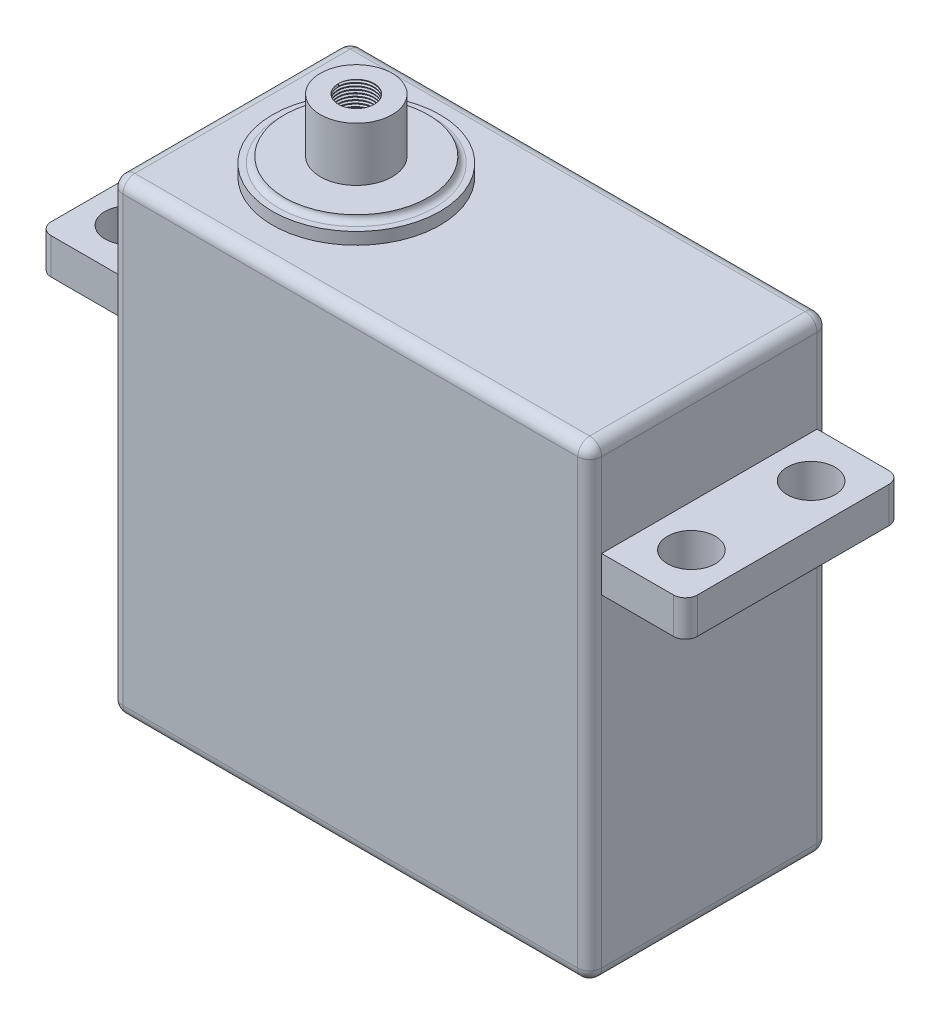
SolidWorks part; units mm, degrees
ref_plane "前视基准面" through (0, 0, 0) normal (0, 0, 1) x (1, 0, 0)
ref_plane "上视基准面" through (0, 0, 0) normal (0, 1, 0) x (1, 0, 0)
ref_plane "右视基准面" through (0, 0, 0) normal (1, 0, 0) x (0, 0, -1)
other "Configuration Table"
sketch "草图1" plane through (0, 0, 0) normal (0, 0, 1) x (1, 0, 0)
  line L1 (-18.7912, 29.9251) -> (21.2088, 29.9251)
  line L2 (-18.7912, 29.9251) -> (-18.7912, -9.0749)
  line L3 (-18.7912, -9.0749) -> (21.2088, -9.0749)
  line L4 (21.2088, 29.9251) -> (21.2088, -9.0749)
  dimension "D1" = 40
  dimension "D2" = 39
extrude "凸台-拉伸1" add sketch "草图1" along normal blind 20
fillet "圆角1" radius 1 12 edges at (21.2088, -9.0749, 10) (21.2088, 29.9251, 10) (1.2088, -9.0749, 0) (21.2088, 10.4251, 0) (1.2088, 29.9251, 0) (-18.7912, 29.9251, 10) (-18.7912, -9.0749, 10) (-18.7912, 10.4251, 0) (1.2088, 29.9251, 20) (21.2088, 10.4251, 20) (1.2088, -9.0749, 20) (-18.7912, 10.4251, 20)
sketch "草图2" plane through (-18.7912, 0, 0) normal (-1, 0, 0) x (0, 0, 1)
  line L1 (19, -8.0749) -> (19, 28.9251) construction
  line L2 (1, 28.9251) -> (1, -8.0749) construction
  line L3 (19, 21.9251) -> (1, 21.9251)
  line L4 (19, 21.9251) -> (19, 18.9251)
  line L5 (19, 18.9251) -> (1, 18.9251)
  line L6 (1, 21.9251) -> (1, 18.9251)
  dimension "D2" = 3
extrude "凸台-拉伸2" add sketch "草图2" along normal blind 7
sketch "草图3" plane through (21.2088, 0, 0) normal (1, 0, 0) x (0, 0, -1)
  line L1 (-1, -8.0749) -> (-1, 28.9251) construction
  line L2 (-19, 28.9251) -> (-19, -8.0749) construction
  line L3 (-1, 21.9251) -> (-19, 21.9251)
  line L4 (-1, 21.9251) -> (-1, 18.9251)
  line L5 (-1, 18.9251) -> (-19, 18.9251)
  line L6 (-19, 21.9251) -> (-19, 18.9251)
  dimension "D2" = 3
extrude "凸台-拉伸3" add sketch "草图3" along normal blind 7
fillet "圆角8" radius 1 1 edges at (28.2088, 20.4251, 1)
fillet "圆角9" radius 1 3 edges at (-25.7912, 20.4251, 1) (-25.7912, 20.4251, 19) (28.2088, 20.4251, 19)
sketch "草图4" plane through (0, 21.9251, 0) normal (0, 1, 0) x (1, 0, 0)
  circle A0 centre (-22.2912, -5) radius 2
extrude "切除-拉伸1" cut sketch "草图4" against normal blind 7
sketch "草图5" plane through (0, 21.9251, 0) normal (0, 1, 0) x (1, 0, 0)
  circle A0 centre (-22.2912, -15) radius 2
extrude "切除-拉伸2" cut sketch "草图5" against normal blind 7
sketch "草图6" plane through (0, 21.9251, 0) normal (0, 1, 0) x (1, 0, 0)
  circle A0 centre (24.7088, -5) radius 2
extrude "切除-拉伸3" cut sketch "草图6" against normal blind 7
sketch "草图8" plane through (0, 21.9251, 0) normal (0, 1, 0) x (1, 0, 0)
  circle A0 centre (24.7088, -15) radius 2
extrude "切除-拉伸4" cut sketch "草图8" against normal blind 7
sketch "草图9" plane through (0, 29.9251, 0) normal (0, 1, 0) x (1, 0, 0)
  circle A0 centre (-8.2912, -10) radius 3
extrude "凸台-拉伸4" add sketch "草图9" along normal blind 6
sketch "草图10" plane through (0, 29.9251, 0) normal (0, 1, 0) x (1, 0, 0)
  circle A0 centre (-8.2912, -10) radius 7
extrude "凸台-拉伸5" add sketch "草图10" along normal blind 1
sketch "草图11" plane through (0, 29.9251, 0) normal (0, 1, 0) x (1, 0, 0)
  circle A0 centre (-8.2912, -10) radius 6
extrude "凸台-拉伸6" add sketch "草图11" along normal blind 2
fillet "圆角11" radius 0.5 2 edges at (-8.2912, 31.9251, 16) (-8.2912, 30.9251, 16)
sketch "草图12" plane through (0, 0, 20) normal (0, 0, 1) x (1, 0, 0)
  line L0 (-2.2912, 31.4251) -> (-14.2912, 31.4251) construction
  line L1 (-14.2912, 31.4251) -> (-2.2912, 31.4251)
  line L2 (-14.2912, 31.4251) -> (-14.2912, 31.9251)
  line L3 (-14.2912, 31.9251) -> (-2.2912, 31.9251)
  line L4 (-2.2912, 31.4251) -> (-2.2912, 31.9251)
  arc A0 (-14.7912, 30.9251) -> (-14.2912, 31.4251) centre (-14.7912, 31.4251) ccw construction
  dimension "D1" = 12
  dimension "D2" = 0.5
extrude "切除-拉伸6" cut sketch "草图12" against normal blind 19
sketch "草图13" plane through (0, 35.9251, 0) normal (0, 1, 0) x (1, 0, 0)
  circle A0 centre (-8.2912, -10) radius 3
extrude "凸台-拉伸7" add sketch "草图13" against normal blind 6
sketch "草图14" plane through (0, 35.9251, 0) normal (0, 1, 0) x (1, 0, 0)
  circle A0 centre (-8.2912, -10) radius 1.5
extrude "切除-拉伸7" cut sketch "草图14" against normal blind 6
thread "螺纹线1" pitch 0.25 method cut profile "螺纹线轮廓1" start angle 0, offset 0, length 6, pitch 0.25, diameter 3
ref_plane "基准面1" through (-9.7912, 35.9251, 10) normal (0, 0, 1) x (-1, 0, 0)
sketch "螺纹线轮廓1" plane through (-9.7912, 35.9251, 10) normal (0, 0, 1) x (-1, 0, 0)
  line L0 (0, 0) -> (0, 0.25) construction
  line L1 (0, 0) -> (0.1353, 0.0781)
  line L2 (0.1353, 0.0781) -> (0.1353, 0.1094)
  line L3 (0.1353, 0.1094) -> (0, 0.1875)
  line L4 (0.1353, 0.0937) -> (0, 0.0937) construction
  line L11 (0, 0) -> (0, 0.1875)
  point P2 (0, 0)
  dimension "Pitch" = 0.25
  dimension "Profile_Angle" = 60
  dimension "Profile_Land" = 0.0312
  dimension "Profile_Height" = 0.1353
